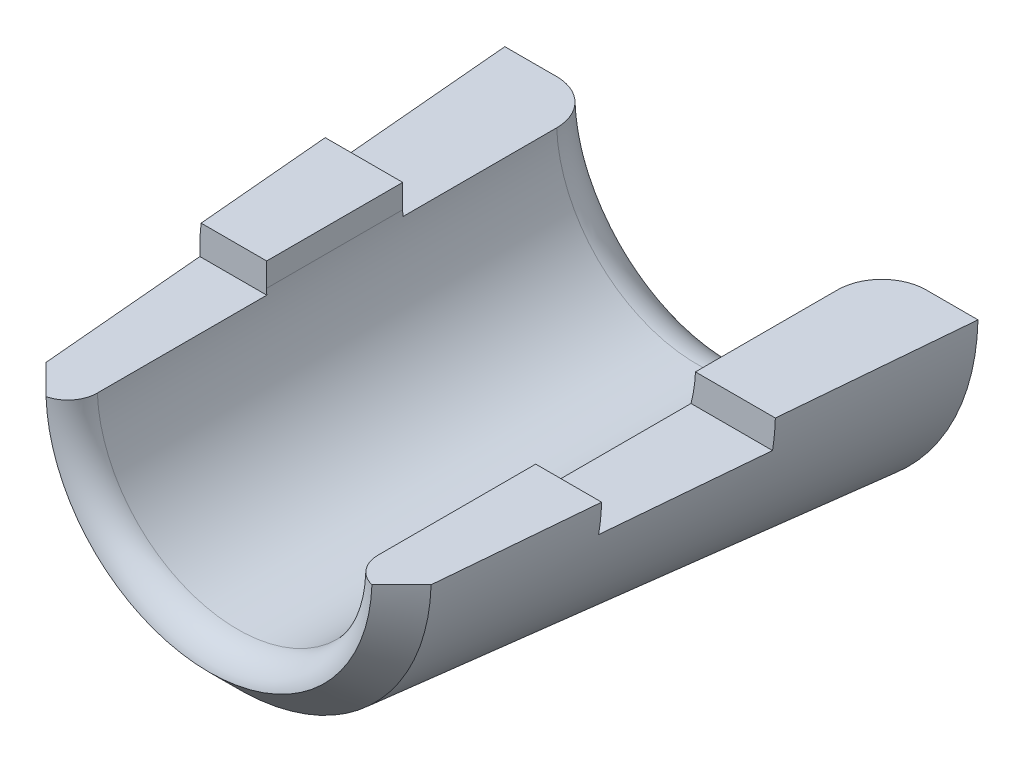
SolidWorks part; units mm, degrees
ref_plane "Front" through (0, 0, 0) normal (0, 0, 1) x (1, 0, 0)
ref_plane "Top" through (0, 0, 0) normal (0, 1, 0) x (1, 0, 0)
ref_plane "Right" through (0, 0, 0) normal (1, 0, 0) x (0, 0, -1)
sketch "Sketch2" plane through (0, 0, 0) normal (1, 0, 0) x (0, 0, -1)
  line L0 (0, 0) -> (-18, 0)
  line L1 (-18, 0) -> (-18, 5.5127)
  line L2 (-18, 5.5127) -> (-17, 6.5127)
  line L3 (-17, 6.5127) -> (0, 8)
  line L5 (0, 8) -> (0, 0)
  line L9 (-18, 5.5127) -> (-18, 6.4252) construction
  line L10 (-18, 6.4252) -> (-17, 6.5127) construction
  line L13 (-18, 0) -> (-20.4063, 0) construction
  dimension "D1" = 45
  dimension "D2" = 16
  dimension "D3" = 1
  dimension "D5" = 18
  dimension "D7" = 5
revolve "Body Revolve1" add sketch "Sketch2" angle 360 about L13
sketch "Sketch3" plane through (0, 0, 0) normal (0, 0, 1) x (1, 0, 0)
  circle A0 centre (0, 0) radius 4.75
  dimension "D1" = 9.5
extrude "Wire Hole Cut" cut sketch "Sketch3" along normal through all
fillet "Front Strain Fillet" radius 1 1 edges at (4.75, 0, 18)
fillet "Rear Strain Fillet" radius 1.5 1 edges at (4.75, 0, 0)
sketch "Sketch5" plane through (0, 0, 0) normal (1, 0, 0) x (0, 0, -1)
  line L0 (-18, 0) -> (-11.5, 0)
  line L2 (-11.5, 0) -> (-6.5, 0) construction
  line L3 (-6.5, 0) -> (0, 0)
  line L4 (-11.5, 0) -> (-11.5, 1)
  line L5 (-11.5, 1) -> (-6.5, 1)
  line L6 (-6.5, 1) -> (-6.5, 0)
  line L7 (-18, 5.5127) -> (-18, 6.4252) construction
  dimension "D1" = 1
  dimension "D2" = 5
extrude "Split Cut 1" cut sketch "Sketch5" against normal through all thin
sketch "Sketch7" plane through (0, 0, 0) normal (1, 0, 0) x (0, 0, -1)
  line L0 (-18, 0) -> (-11.5, 0)
  line L1 (-11.5, 0) -> (-11.5, -1)
  line L2 (-11.5, -1) -> (-6.5, -1)
  line L3 (-6.5, -1) -> (-6.5, 0)
  line L4 (-6.5, 0) -> (0, 0)
  line L5 (-11.5, 0) -> (-11.5, 1) construction
extrude "Split Cut 2" cut sketch "Sketch7" along normal through all thin
sketch "Sketch6" plane through (0, 0, 0) normal (0, 0, 1) x (1, 0, 0)
  line L0 (-4.75, 0) -> (-4.75, 2)
  line L2 (-4.75, 2) -> (4.75, 2)
  line L3 (4.75, 2) -> (4.75, 0)
  circle A0 centre (0, 0) radius 4.75 construction
  arc A1 (-4.75, 0) -> (4.75, 0) centre (0, 0) ccw
  dimension "D1" = 2
extrude "Wire Insert Notch" cut sketch "Sketch6" along normal through all
equation "\"Wire OD\" = 9.5mm"
equation "\"D1@Sketch3\"=\"Wire OD\""
